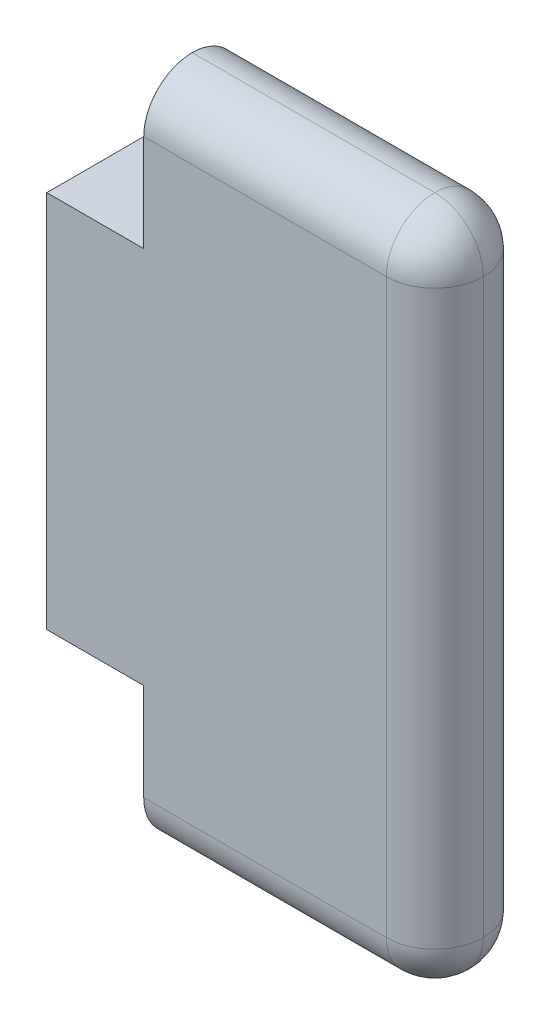
SolidWorks part; units mm, degrees
ref_plane "Front Plane" through (0, 0, 0) normal (0, 0, 1) x (1, 0, 0)
ref_plane "Top Plane" through (0, 0, 0) normal (0, 1, 0) x (1, 0, 0)
ref_plane "Right Plane" through (0, 0, 0) normal (1, 0, 0) x (0, 0, -1)
sketch "Sketch1" plane through (0, 0, 0) normal (0, 0, 1) x (1, 0, 0)
  line L0 (0, -19.5) -> (0, 19.5)
  line L1 (0, 19.5) -> (10, 19.5)
  line L2 (10, 19.5) -> (10, 34.5)
  line L3 (10, 34.5) -> (40, 34.5)
  line L4 (40, 34.5) -> (40, -34.5)
  line L5 (40, -34.5) -> (10, -34.5)
  line L6 (10, -34.5) -> (10, -19.5)
  line L7 (10, -19.5) -> (0, -19.5)
  point P8 (0, 0)
  point P10 (40, 0)
  dimension "D1" = 69
  dimension "D2" = 39
  dimension "D3" = 10
  dimension "D4" = 10
  dimension "D5" = 30
extrude "Boss-Extrude1" add sketch "Sketch1" along normal blind 10
fillet "Fillet1" radius 5 4 edges at (40, -34.5, 5) (40, 0, 10) (40, 34.5, 5) (40, 0, 0)
fillet "Fillet2" radius 5 8 edges at (38.5355, 33.0355, 1.4645) (38.5355, 33.0355, 8.5355) (38.5355, -33.0355, 1.4645) (38.5355, -33.0355, 8.5355) (22.5, 34.5, 0) (22.5, 34.5, 10) (22.5, -34.5, 0) (22.5, -34.5, 10)
